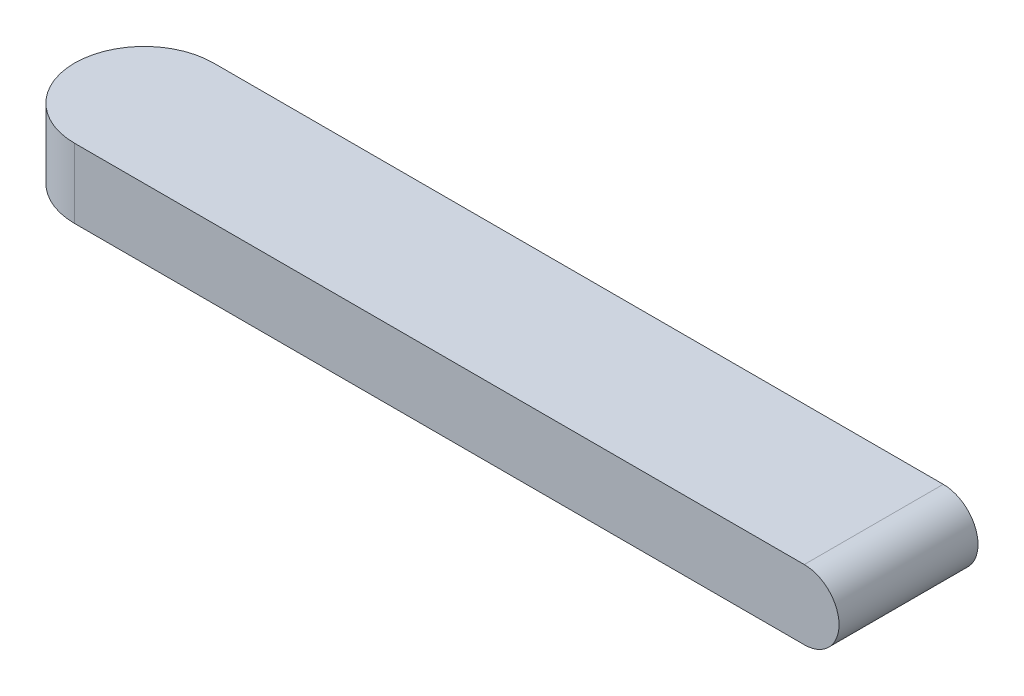
SolidWorks part; units mm, degrees
ref_plane "Front Plane" through (0, 0, 0) normal (0, 0, 1) x (1, 0, 0)
ref_plane "Top Plane" through (0, 0, 0) normal (0, 1, 0) x (1, 0, 0)
ref_plane "Right Plane" through (0, 0, 0) normal (1, 0, 0) x (0, 0, -1)
sketch "Sketch1" plane through (0, 0, 0) normal (0, 0, 1) x (1, 0, 0)
  line L1 (6, -0.5) -> (-6, -0.5)
  line L2 (6, -0.5) -> (6, 0.5)
  line L3 (6, 0.5) -> (-6, 0.5)
  line L4 (-6, -0.5) -> (-6, 0.5)
  line L5 (6, -0.5) -> (-6, 0.5) construction
  line L6 (6, 0.5) -> (-6, -0.5) construction
  point P0 (0, 0)
  dimension "D1" = 12
  dimension "D2" = 1
extrude "Boss-Extrude1" add sketch "Sketch1" along normal blind 2
fillet "Fillet1" 2 edges at (-6, 0, 2) (-6, 0, 0) type full round first side face at (0, 0, 2) second side face at (0, 0, 0) middle face at (-6, 0, 1)
fillet "Fillet2" 2 edges at (6, 0.5, 1) (6, -0.5, 1) type full round first side face at (0.25, 0.5, 1) second side face at (0.25, -0.5, 1) middle face at (6, 0, 1)
